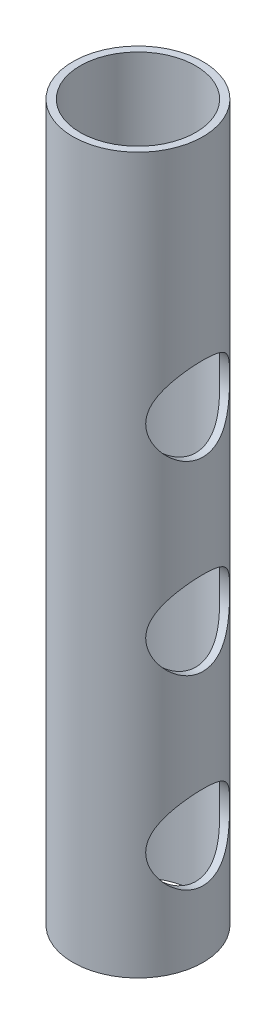
SolidWorks part; units mm, degrees
material "PTFE (general)"
ref_plane "Front Plane" through (0, 0, 0) normal (0, 0, 1) x (1, 0, 0)
ref_plane "Top Plane" through (0, 0, 0) normal (0, 1, 0) x (1, 0, 0)
ref_plane "Right Plane" through (0, 0, 0) normal (1, 0, 0) x (0, 0, -1)
sketch "Sketch1" plane through (0, 0, 0) normal (0, 1, 0) x (1, 0, 0)
  circle A0 centre (0, 0) radius 17.875
  circle A1 centre (0, 0) radius 15.875
  dimension "D1" = 2
  dimension "D2" = 31.75
extrude "Boss-Extrude1" add sketch "Sketch1" along normal blind 196.5
sketch "Sketch2" plane through (0, 0, 0) normal (1, 0, 0) x (0, 0, -1)
  line L0 (15.875, 196.5) -> (-15.875, 196.5) construction
  circle A0 centre (0, 131.8) radius 11.53
  circle A1 centre (0, 80.8) radius 11.53
  circle A2 centre (0, 29.8) radius 11.53
  dimension "D2" = 23.06
  dimension "D3" = 23.06
  dimension "D4" = 23.06
  dimension "D1" = 64.7
  dimension "D5" = 51
  dimension "D6" = 51
extrude "Cut-Extrude1" cut sketch "Sketch2" along normal through all
